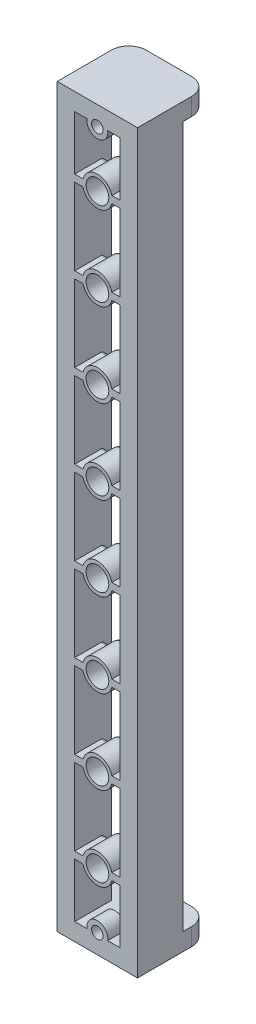
SolidWorks part; units mm, degrees
ref_plane "Front Plane" through (0, 0, 0) normal (0, 0, 1) x (1, 0, 0)
ref_plane "Top Plane" through (0, 0, 0) normal (0, 1, 0) x (1, 0, 0)
ref_plane "Right Plane" through (0, 0, 0) normal (1, 0, 0) x (0, 0, -1)
sketch "Sketch1" plane through (0, 0, 0) normal (0, 0, 1) x (1, 0, 0)
  line L0 (6.5, 100.5) -> (6.5, -100.5)
  line L1 (-11.5, 105.5) -> (11.5, 105.5)
  line L2 (-11.5, 105.5) -> (-11.5, -105.5)
  line L3 (-11.5, -105.5) -> (11.5, -105.5)
  line L4 (11.5, 105.5) -> (11.5, -105.5)
  line L5 (-11.5, 105.5) -> (11.5, -105.5) construction
  line L6 (-11.5, -105.5) -> (11.5, 105.5) construction
  line L7 (-6.5, -100.5) -> (6.5, -100.5)
  line L8 (-6.5, 100.5) -> (-6.5, -100.5)
  line L9 (-6.5, 100.5) -> (6.5, 100.5)
  point P0 (0, 0)
  dimension "D1" = 23
  dimension "D2" = 211
  dimension "D3" = 5
extrude "Boss-Extrude1" add sketch "Sketch1" along normal blind 13
sketch "Sketch7" plane through (0, 0, 13) normal (0, 0, 1) x (1, 0, 0)
  line L0 (0.0237, 87.6593) -> (0.0237, 80.2815) construction
  line L5 (-3.3958, 83) -> (-7.3958, 83)
  line L6 (7.4431, 85) -> (3.4431, 85)
  line L11 (-3.3958, 85) -> (-3.3958, 83)
  line L12 (-7.3958, 85) -> (-3.3958, 85)
  line L13 (3.4431, 85) -> (3.4431, 83)
  line L14 (3.4431, 83) -> (7.4431, 83)
  line L15 (7.4431, 83) -> (7.4431, 85)
  line L16 (-7.3958, 83) -> (-7.3958, 85)
  line L18 (11.5, 105.5) -> (-11.5, 105.5) construction
  circle A0 centre (0.0237, 84) radius 3.25
  circle A1 centre (0.0237, 84) radius 4.25
  point P5 (7.4431, 84)
  dimension "D1" = 6.5
  dimension "D2" = 8.5
  dimension "D3" = 20.5
  dimension "D4" = 4
  dimension "D5" = 2
extrude "Boss-Extrude5" add sketch "Sketch7" against normal blind 8.5
fillet "Fillet4" radius 1 6 edges at (-5.3035, 83, 4.5) (5.3272, 85, 4.5) (-5.3035, 85, 4.5) (0.0237, 88.25, 4.5) (5.3272, 83, 4.5) (0.0237, 79.75, 4.5)
pattern_linear "LPattern7" count 8 spacing 24 along (0, -1, 0) of "Boss-Extrude5", "Fillet4"
sketch "Sketch11" plane through (0, -105.5, 0) normal (0, -1, 0) x (-1, 0, 0)
  line L0 (6.5, -2.0313) -> (6.5, 0)
  line L2 (11.5, 0) -> (-11.5, 0) construction
  line L3 (11.5, -13) -> (11.5, 0) construction
  line L4 (8.5313, 0) -> (6.5, 0)
  line L5 (0, 0) -> (0, -13) construction
  line L6 (11.5, -13) -> (-11.5, -13) construction
  line L7 (-8.5313, 0) -> (-6.5, 0)
  line L8 (-6.5, -2.0313) -> (-6.5, 0)
  arc A0 (6.5, -2.0313) -> (8.5313, 0) centre (6.5, 0) ccw
  arc A1 (-6.5, -2.0313) -> (-8.5313, 0) centre (-6.5, 0) cw
  dimension "D1" = 5
ref_plane "Plane1" through (0, 0, 0) normal (-1, 0, 0) x (0, 0, 1)
ref_plane "Plane2" through (0, 0, 0) normal (0, 1, 0) x (1, 0, 0)
sketch "Sketch15" plane through (0, 105.5, 0) normal (0, 1, 0) x (1, 0, 0)
  line L0 (11.5, 0) -> (-11.5, 0)
  line L4 (11.5, 0) -> (4.4687, 0)
  line L5 (-11.5, 0) -> (-11.5, -13)
  line L6 (-11.5, -13) -> (11.5, -13)
  line L7 (11.5, -13) -> (11.5, 0)
  line L9 (-11.5, 0) -> (-11.5, -13)
  line L10 (-11.5, -13) -> (11.5, -13)
  line L11 (11.5, -13) -> (11.5, 0)
  line L21 (-6.5, 0) -> (-6.5, -2.0313)
  line L25 (-8.5313, 0) -> (-11.5, 0)
  line L26 (6.5, -2.0313) -> (6.5, 0)
  line L27 (6.5, 0) -> (-6.5, 0)
  arc A2 (-8.5313, 0) -> (-6.5, -2.0313) centre (-6.5, 0) ccw
  arc A6 (6.5, -2.0313) -> (4.4687, 0) centre (6.5, 0) ccw
  dimension "D1" = 0
extrude "Boss-Extrude8" add sketch "Sketch15" along normal blind 5
mirror "Mirror5" about plane through (0, 0, 0) normal (0, 1, 0) of "Boss-Extrude8"
sketch "Sketch19" plane through (-11.5, 0, 0) normal (-1, 0, 0) x (0, 0, 1)
  line L0 (13, 105.5) -> (0, 105.5) construction
  line L1 (13, 110.5) -> (13, -110.5) construction
  line L2 (0, 110.5) -> (0, -110.5) construction
  line L3 (0, 110.5) -> (13, 110.5) construction
  line L4 (13, 82.75) -> (0, 82.75) construction
  line L5 (13, 84.75) -> (0, 84.75) construction
  line L6 (0, 98.125) -> (13, 98.125) construction
  line L7 (9.5485, 103.625) -> (3.5485, 103.625)
  line L8 (3.5485, 103.625) -> (3.5485, 98.625)
  line L9 (3.5485, 98.625) -> (9.5485, 103.625)
  line L10 (11.5, 103.625) -> (11.5, 98.625)
  line L11 (11.5, 98.625) -> (5.5, 98.625)
  line L12 (5.5, 98.625) -> (11.5, 103.625)
  line L13 (0, 92.125) -> (13, 92.125) construction
  line L14 (0, 0) -> (13, 0) construction
  line L15 (11.5, 97.625) -> (5.5, 97.625)
  line L16 (11.5, 92.625) -> (11.5, 97.625)
  line L17 (5.5, 97.625) -> (11.5, 92.625)
  line L18 (3.5485, 92.625) -> (3.5485, 97.625)
  line L19 (9.5485, 92.625) -> (3.5485, 92.625)
  line L20 (3.5485, 97.625) -> (9.5485, 92.625)
  line L21 (11.5, 91.625) -> (11.5, 86.625)
  line L22 (5.5, 86.625) -> (11.5, 91.625)
  line L23 (11.5, 86.625) -> (5.5, 86.625)
  line L24 (9.5485, 91.625) -> (3.5485, 91.625)
  line L25 (3.5485, 86.625) -> (9.5485, 91.625)
  line L26 (3.5485, 91.625) -> (3.5485, 86.625)
  dimension "D1" = 5
  dimension "D2" = 5
  dimension "D3" = 2
  dimension "D4" = 1.2493
  dimension "D5" = 1.5
  dimension "D6" = 0.5
  dimension "D7" = 1.875
  dimension "D8" = 6
  dimension "D9" = 0.5
extrude "Cut-Extrude7" [suppressed] cut sketch "Sketch19" against normal blind 5
pattern_linear "LPattern10" [suppressed] count 9 spacing 23.8
ref_plane "Plane3" through (0, 0, 0) normal (-1, 0, 0) x (0, 0, 1)
mirror "Mirror7" [suppressed] about plane through (0, 0, 0) normal (-1, 0, 0)
sketch "Sketch22" plane through (0, 0, 0) normal (0, 0, -1) x (-1, 0, 0)
  line L0 (11.5, 110.5) -> (11.5, -110.5) construction
  line L1 (-11.5, 110.5) -> (11.5, 110.5)
  line L2 (-11.5, 110.5) -> (-11.5, 105.5)
  line L3 (-11.5, 105.5) -> (11.5, 105.5)
  line L4 (11.5, 110.5) -> (11.5, 105.5)
  line L6 (-11.5, -110.5) -> (11.5, -110.5)
  line L7 (-11.5, -110.5) -> (-11.5, -105.5)
  line L8 (-11.5, -105.5) -> (11.5, -105.5)
  line L9 (11.5, -110.5) -> (11.5, -105.5)
  dimension "D1" = 5
  dimension "D2" = 5
extrude "Cut-Extrude9" cut sketch "Sketch22" against normal through all
sketch "Sketch21" plane through (0, 0, 13) normal (0, 0, 1) x (1, 0, 0)
  line L1 (6.5, 100.5) -> (-6.5, 100.5) construction
  line L6 (-4.7323, 0) -> (3.9666, 0) construction
  line L11 (-2.5, 100.5) -> (2.5, 100.5)
  line L12 (-2.5, 100.5) -> (-2.5, 103.5)
  line L13 (-2.5, 103.5) -> (2.5, 103.5)
  line L14 (2.5, 100.5) -> (2.5, 103.5)
  line L15 (11.5, 105.5) -> (-11.5, 105.5) construction
  line L16 (-2.5, -103.5) -> (2.5, -103.5)
  line L17 (2.5, -100.5) -> (2.5, -103.5)
  line L18 (-2.5, -100.5) -> (2.5, -100.5)
  line L19 (-2.5, -100.5) -> (-2.5, -103.5)
  point P18 (0, 105.5)
  point P19 (0, 103.5)
  dimension "D3" = 3
  dimension "D4" = 5
extrude "Cut-Extrude8" [suppressed] cut sketch "Sketch21" against normal blind 5
fillet "Fillet7" [suppressed] radius 1
sketch "Sketch23" plane through (0, 0, 0) normal (0, 0, -1) x (-1, 0, 0)
  line L0 (11.5, 105.5) -> (11.5, -105.5) construction
  line L1 (-11.5, 105.5) -> (11.5, 105.5)
  line L2 (-11.5, 105.5) -> (-11.5, 100.5)
  line L3 (-11.5, 100.5) -> (11.5, 100.5)
  line L4 (11.5, 105.5) -> (11.5, 100.5)
  line L5 (-6.5, 100.5) -> (6.5, 100.5) construction
  line L6 (6.5, -100.5) -> (-6.5, -100.5) construction
  line L7 (-11.5, -105.5) -> (11.5, -105.5)
  line L8 (-11.5, -105.5) -> (-11.5, -100.5)
  line L9 (-11.5, -100.5) -> (11.5, -100.5)
  line L10 (11.5, -105.5) -> (11.5, -100.5)
extrude "Boss-Extrude9" add sketch "Sketch23" along normal blind 7.5
fillet "Fillet8" radius 5 4 edges at (11.5, 103, -7.5) (-11.5, 103, -7.5) (-11.5, -103, -7.5) (11.5, -103, -7.5)
sketch "Sketch25" plane through (0, -105.5, 0) normal (0, -1, 0) x (1, 0, 0)
  line L4 (-11.5, 13) -> (-11.5, -2.5) construction
  line L5 (-11.5, 13) -> (11.5, 13) construction
  line L6 (-9, -0.5) -> (-6, -0.5)
  line L7 (-6, -0.5) -> (-6, 2.5)
  line L8 (0, 2.725) -> (0, -1.8067) construction
  line L9 (6, -0.5) -> (6, 2.5)
  line L10 (9, -0.5) -> (6, -0.5)
  arc A0 (-6, 2.5) -> (-9, -0.5) centre (-6, -0.5) ccw
  arc A1 (6, 2.5) -> (9, -0.5) centre (6, -0.5) cw
  dimension "D1" = 13.5
  dimension "D2" = 5.5
  dimension "D3" = 3
extrude "Cut-Extrude11" cut sketch "Sketch25" against normal up to surface (201 mm away) from surface at -5 up to face at (0, 100.5, 0.3929) starting at face at (0, -100.5, 0.3929)
sketch "Sketch26" plane through (0, 0, 13) normal (0, 0, 1) x (1, 0, 0)
  line L0 (0, 100) -> (0, -100) construction
  circle A0 centre (0, -100) radius 3
  circle A1 centre (0, 100) radius 3
  point P4 (0, 0)
  dimension "D2" = 6
  dimension "D1" = 200
extrude "Boss-Extrude10" add sketch "Sketch26" against normal blind 5
sketch "Sketch27" plane through (0, 0, 13) normal (0, 0, 1) x (1, 0, 0)
  circle A0 centre (0, -100) radius 1.65
  circle A1 centre (0, 100) radius 1.65
  dimension "D1" = 3.3
extrude "Cut-Extrude12" cut sketch "Sketch27" against normal through all
